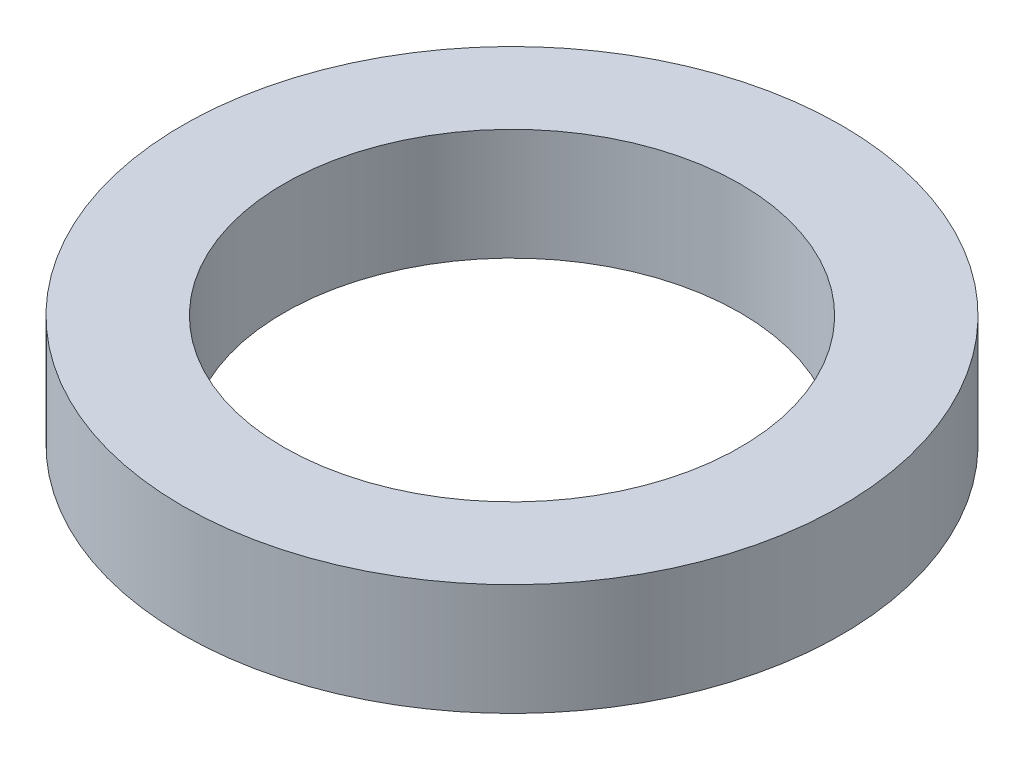
SolidWorks part; units mm, degrees
ref_plane "Front Plane" through (0, 0, 0) normal (0, 0, 1) x (1, 0, 0)
ref_plane "Top Plane" through (0, 0, 0) normal (0, 1, 0) x (1, 0, 0)
ref_plane "Right Plane" through (0, 0, 0) normal (1, 0, 0) x (0, 0, -1)
sketch "Sketch1" plane through (0, 0, 0) normal (0, 1, 0) x (1, 0, 0)
  circle A0 centre (0, 0) radius 32.5
  dimension "FLANGE_OD" = 65
extrude "Boss-Extrude1" add sketch "Sketch1" along normal blind 11
sketch "Sketch2" plane through (0, 0, 0) normal (0, 1, 0) x (1, 0, 0)
  circle A0 centre (0, 0) radius 22.5
  dimension "BORE_D" = 45
extrude "Cut-Extrude1" cut sketch "Sketch2" along normal through all
sketch "Sketch3" plane through (0, 11, 0) normal (0, 1, 0) x (1, 0, 0)
  circle A0 centre (0, 0) radius 13.8011 construction
  circle A1 centre (-13.8011, 0) radius 1.5531
  dimension "BOLT_D" = 3.1062
  dimension "BOLT_PCD" = 27.6021
extrude "Cut-Extrude2" cut sketch "Sketch3" against normal blind 8.4489 rebuild error yes
pattern_circular "CirPattern1" count 4 over 360 rebuild error yes
